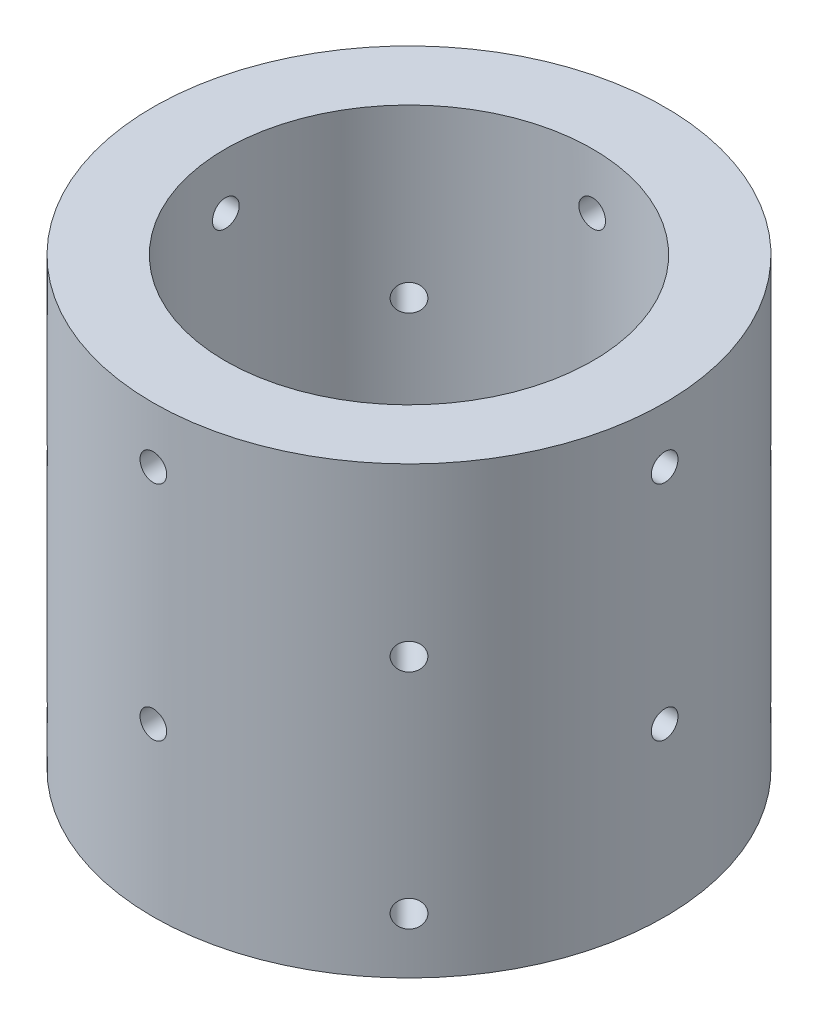
SolidWorks part; units mm, degrees
ref_plane "Спереди" through (0, 0, 0) normal (0, 0, 1) x (1, 0, 0)
ref_plane "Сверху" through (0, 0, 0) normal (0, 1, 0) x (1, 0, 0)
ref_plane "Справа" through (0, 0, 0) normal (1, 0, 0) x (0, 0, -1)
sketch "Эскиз1" plane through (0, 0, 0) normal (0, 1, 0) x (1, 0, 0)
  circle A0 centre (0, 0) radius 23
  dimension "D1" = 46
extrude "Бобышка-Вытянуть1" add sketch "Эскиз1" along normal blind 5
sketch "Эскиз2" plane through (0, 5, 0) normal (0, 1, 0) x (1, 0, 0)
  circle A0 centre (0, 0) radius 23
  circle A1 centre (0, 0) radius 16.5
  circle A2 centre (0, 0) radius 23 construction
  dimension "D1" = 33
  dimension "D2" = 0
extrude "Бобышка-Вытянуть2" add sketch "Эскиз2" along normal blind 35
sketch "Эскиз3" plane through (0, 0, 0) normal (1, 0, 0) x (0, 0, -1)
  line L0 (-23, 20) -> (28.0263, 20) construction
  line L1 (-23, 40) -> (-23, 0) construction
  line L2 (16.5, 40) -> (-16.5, 40) construction
  circle A1 centre (0, 35) radius 1.2
  dimension "D1" = 2.4
  dimension "D2" = 5
extrude "Вырез-Вытянуть1" cut sketch "Эскиз3" against normal through all
ref_plane "Плоскость1" through (0, 0, 0) normal (0.7071, 0, 0.7071) x (0, -1, 0)
sketch "Эскиз4" plane through (0, 0, 0) normal (0.7071, 0, 0.7071) x (0, -1, 0)
  line L0 (-20, 23) -> (-20, -30.0625) construction
  line L1 (0, 23) -> (-40, 23) construction
  line L3 (0, -23) -> (0, 23) construction
  circle A1 centre (-5, 0) radius 1.2
  dimension "D1" = 5
  dimension "D2" = 2.4
extrude "Вырез-Вытянуть2" cut sketch "Эскиз4" against normal through all from offset 16.3 offset against normal yes
pattern_circular "Круговой массив1" count 4 over 360 about axis through (0, 5, 0) along (0, -1, 0) of "Вырез-Вытянуть2"
pattern_circular "Круговой массив2" count 4 over 360 about axis through (0, 5, 0) along (0, -1, 0) of "Вырез-Вытянуть1"
pattern_linear "Линейный массив3" count 2 spacing 20 along (0, 1, 0) of "Круговой массив1"
pattern_linear "Линейный массив4" count 2 spacing 20 along (0, -1, 0) of "Круговой массив2"
